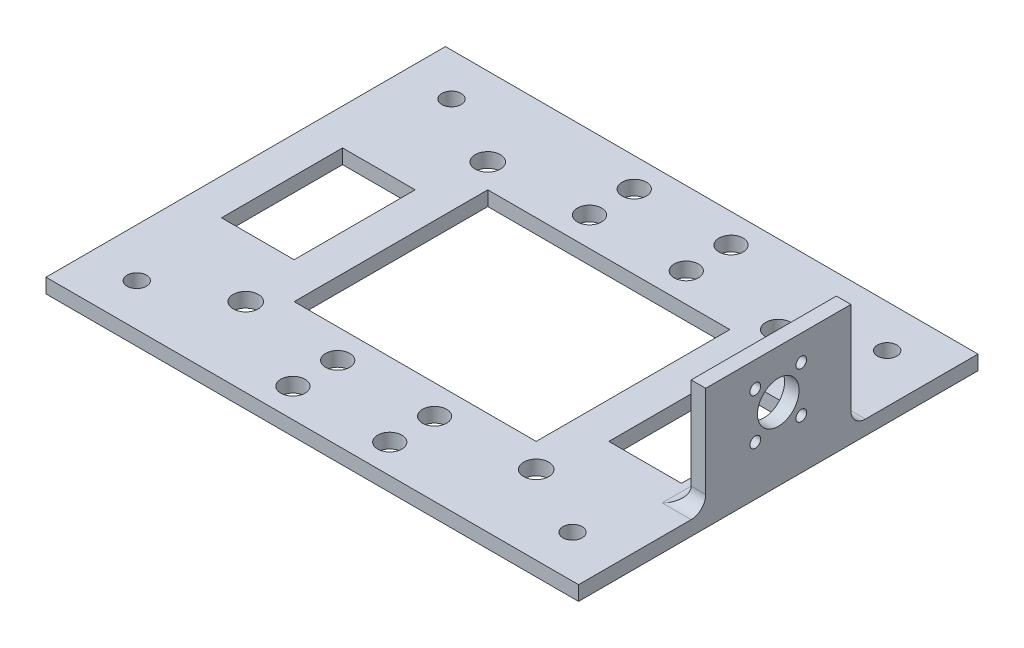
SolidWorks part; units mm, degrees
material "ABS"
ref_plane "Front Plane" through (0, 0, 0) normal (0, 0, 1) x (1, 0, 0)
ref_plane "Top Plane" through (0, 0, 0) normal (0, 1, 0) x (1, 0, 0)
ref_plane "Right Plane" through (0, 0, 0) normal (1, 0, 0) x (0, 0, -1)
sketch "Sketch1" plane through (0, 0, 0) normal (0, 1, 0) x (1, 0, 0)
  line L0 (45, 41.25) -> (45, 32.5) construction
  line L1 (-55, -41.25) -> (55, -41.25)
  line L2 (-55, -41.25) -> (-55, 41.25)
  line L3 (-55, 41.25) -> (55, 41.25)
  line L4 (55, -41.25) -> (55, 41.25)
  line L5 (-55, -41.25) -> (55, 41.25) construction
  line L6 (-55, 41.25) -> (55, -41.25) construction
  line L7 (-13.75, 0) -> (13.75, 0) construction
  line L8 (0, -13.75) -> (0, 13.75) construction
  line L9 (-25, -20) -> (-30, -20) construction
  line L10 (-25, -20) -> (25, -20)
  line L11 (-25, -20) -> (-25, 20)
  line L12 (-25, 20) -> (25, 20)
  line L13 (25, -20) -> (25, 20)
  line L14 (-25, -20) -> (25, 20) construction
  line L15 (-25, 20) -> (25, -20) construction
  line L16 (-30, -20) -> (-30, -25) construction
  line L18 (-45, 32.5) -> (45, 32.5) construction
  line L19 (-45, 32.5) -> (-45, -32.5) construction
  line L20 (-45, -32.5) -> (45, -32.5) construction
  line L21 (45, 32.5) -> (45, -32.5) construction
  line L22 (-45, 32.5) -> (45, -32.5) construction
  line L23 (-45, -32.5) -> (45, 32.5) construction
  circle A0 centre (45, 32.5) radius 2
  circle A1 centre (45, -32.5) radius 2
  circle A2 centre (-45, -32.5) radius 2
  circle A3 centre (-45, 32.5) radius 2
  circle A4 centre (-30, -25) radius 2.6
  circle A5 centre (30, -25) radius 2.6
  circle A6 centre (-30, 25) radius 2.6
  circle A7 centre (30, 25) radius 2.6
  point P0 (0, 0)
  point P19 (0, 0)
  point P33 (0, 0)
  dimension "D5" = 4
  dimension "D10" = 5.2
  dimension "D1" = 110
  dimension "D2" = 82.5
  dimension "D3" = 90
  dimension "D4" = 65
  dimension "D6" = 50
  dimension "D7" = 40
  dimension "D8" = 5
  dimension "D9" = 5
extrude "Boss-Extrude1" add sketch "Sketch1" along normal blind 1.5 and the other way blind 1.5
sketch "Sketch2" plane through (55, 0, 0) normal (1, 0, 0) x (0, 0, -1)
  line L0 (-41.25, -1.5) -> (41.25, -1.5) construction
  line L1 (-15, -1.5) -> (15, -1.5)
  line L2 (-15, -1.5) -> (-15, 23.5)
  line L3 (-15, 23.5) -> (15, 23.5)
  line L4 (15, -1.5) -> (15, 23.5)
  line L5 (0, 23.5) -> (0, 13.5) construction
  line L6 (0, 13.5) -> (-4.75, 13.5) construction
  line L7 (-4.75, 13.5) -> (-4.75, 18.25) construction
  circle A0 centre (0, 13.5) radius 4.3
  circle A1 centre (-4.75, 18.25) radius 1.1
  circle A2 centre (4.75, 18.25) radius 1.1
  circle A3 centre (4.75, 8.75) radius 1.1
  circle A4 centre (-4.75, 8.75) radius 1.1
  dimension "D7" = 8.6
  dimension "D8" = 2.2
  dimension "D1" = 15
  dimension "D2" = 15
  dimension "D3" = 25
  dimension "D4" = 4.75
  dimension "D5" = 10
  dimension "D6" = 4.75
extrude "Boss-Extrude2" add sketch "Sketch2" against normal blind 3
fillet "Fillet1" radius 3 3 edges at (53.5, 1.5, 15) (53.5, 1.5, -15) (52, 1.5, 0)
sketch "Sketch3" plane through (0, 0, 0) normal (0, 1, 0) x (1, 0, 0)
  line L0 (0, 0) -> (40, 0) construction
  line L1 (0, -13.75) -> (0, 13.75) construction
  line L2 (47.5, -12.5) -> (32.5, -12.5)
  line L3 (47.5, -12.5) -> (47.5, 12.5)
  line L4 (47.5, 12.5) -> (32.5, 12.5)
  line L5 (32.5, -12.5) -> (32.5, 12.5)
  line L6 (47.5, -12.5) -> (32.5, 12.5) construction
  line L7 (47.5, 12.5) -> (32.5, -12.5) construction
  line L8 (-47.5, 12.5) -> (-32.5, -12.5) construction
  line L9 (-47.5, -12.5) -> (-32.5, 12.5) construction
  line L10 (-32.5, -12.5) -> (-32.5, 12.5)
  line L11 (-47.5, 12.5) -> (-32.5, 12.5)
  line L12 (-47.5, -12.5) -> (-47.5, 12.5)
  line L13 (-47.5, -12.5) -> (-32.5, -12.5)
  line L14 (-48, -31.25) -> (-48, -18.75) construction
  line L15 (-55, -41.25) -> (55, -41.25) construction
  line L16 (-55, 41.25) -> (-55, -41.25) construction
  line L17 (-13.75, 0) -> (13.75, 0) construction
  line L18 (-10, -35.25) -> (-10, -26) construction
  line L19 (-25, -20) -> (25, -20) construction
  circle A0 centre (-48, -31.25) radius 2.5 construction
  circle A1 centre (-48, -18.75) radius 2.5 construction
  circle A2 centre (48, -18.75) radius 2.5 construction
  circle A3 centre (48, -31.25) radius 2.5 construction
  circle A4 centre (-48, 18.75) radius 2.5 construction
  circle A5 centre (-48, 31.25) radius 2.5 construction
  circle A6 centre (48, 18.75) radius 2.5 construction
  circle A7 centre (48, 31.25) radius 2.5 construction
  circle A8 centre (-10, -35.25) radius 2.5
  circle A9 centre (-10, -26) radius 2.5
  circle A10 centre (10, -26) radius 2.5
  circle A11 centre (10, -35.25) radius 2.5
  circle A12 centre (-10, 35.25) radius 2.5
  circle A13 centre (-10, 26) radius 2.5
  circle A14 centre (10, 26) radius 2.5
  circle A15 centre (10, 35.25) radius 2.5
  dimension "D4" = 5
  dimension "D5" = 5
  dimension "D9" = 5
  dimension "D10" = 5
  dimension "D1" = 40
  dimension "D2" = 15
  dimension "D3" = 25
  dimension "D6" = 12.5
  dimension "D7" = 10
  dimension "D8" = 7
  dimension "D11" = 6
  dimension "D12" = 6
  dimension "D13" = 45
extrude "Zip tie holes and weight reduction" cut sketch "Sketch3" against normal through all both and the other way through all
